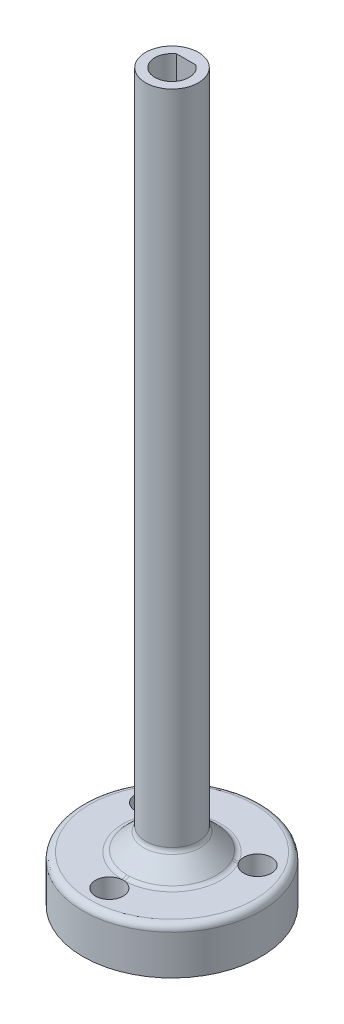
SolidWorks part; units mm, degrees
ref_plane "Front Plane" through (0, 0, 0) normal (0, 0, 1) x (1, 0, 0)
ref_plane "Top Plane" through (0, 0, 0) normal (0, 1, 0) x (1, 0, 0)
ref_plane "Right Plane" through (0, 0, 0) normal (1, 0, 0) x (0, 0, -1)
sketch "Sketch1" plane through (0, 0, 0) normal (0, 1, 0) x (1, 0, 0)
  line L2 (0, -13.5) -> (0, -9.5) construction
  circle A0 centre (0, 0) radius 2.75
  circle A1 centre (0, 0) radius 13.5
  circle A2 centre (0, 0) radius 4
  circle A3 centre (0, -9.5) radius 2.1
  circle A4 centre (-8.2272, 4.75) radius 2.1
  circle A5 centre (8.2272, 4.75) radius 2.1
  point P19 (0, 0)
  dimension "D2" = 27
  dimension "D3" = 5.5
  dimension "D1" = 8
  dimension "D6" = 4.2
  dimension "D4" = 9.5
  dimension "D7" = 3
extrude "Boss-Extrude1" add sketch "Sketch1" along normal blind 7 contours A1 A5 A4 A3 A2 | A2 A0 | A0 | A0 region at (0, 0, 0) region at (-13.1182, 0, 0) region at (-3.8869, 0, 0)
extrude "Boss-Extrude2" add sketch "Sketch1<3>" along normal blind 103 from surface contours A2 A0 | A0 | A0 region at (0, 0, 0) region at (-3.8869, 0, 0) starting at face at (0, 7, 11.6)
sketch "Sketch1<3>" plane through (0, 0, 0) normal (0, 1, 0) x (1, 0, 0) same geometry as "Sketch1"
sketch "Sketch2" plane through (0, 110, 0) normal (0, 1, 0) x (1, 0, 0)
  line L0 (-1.462, 2.15) -> (1.462, 2.15)
  arc A0 (-1.462, 2.15) -> (1.462, 2.15) centre (0, 0) ccw
  dimension "D2" = 2.15
  dimension "D1" = 2.6
extrude "Cut-Extrude1" cut sketch "Sketch2" against normal blind 17
chamfer "Chamfer1" distance 3 angle 45 1 edges at (0, 7, 4)
fillet "Fillet3" radius 1 3 edges at (0, 7, 7) (0, 10, 4) (0, 7, 13.5)
chamfer "Chamfer2" distance 2 angle 45 2 edges at (0, 93, -2.15) (0, 93, 2.6)
